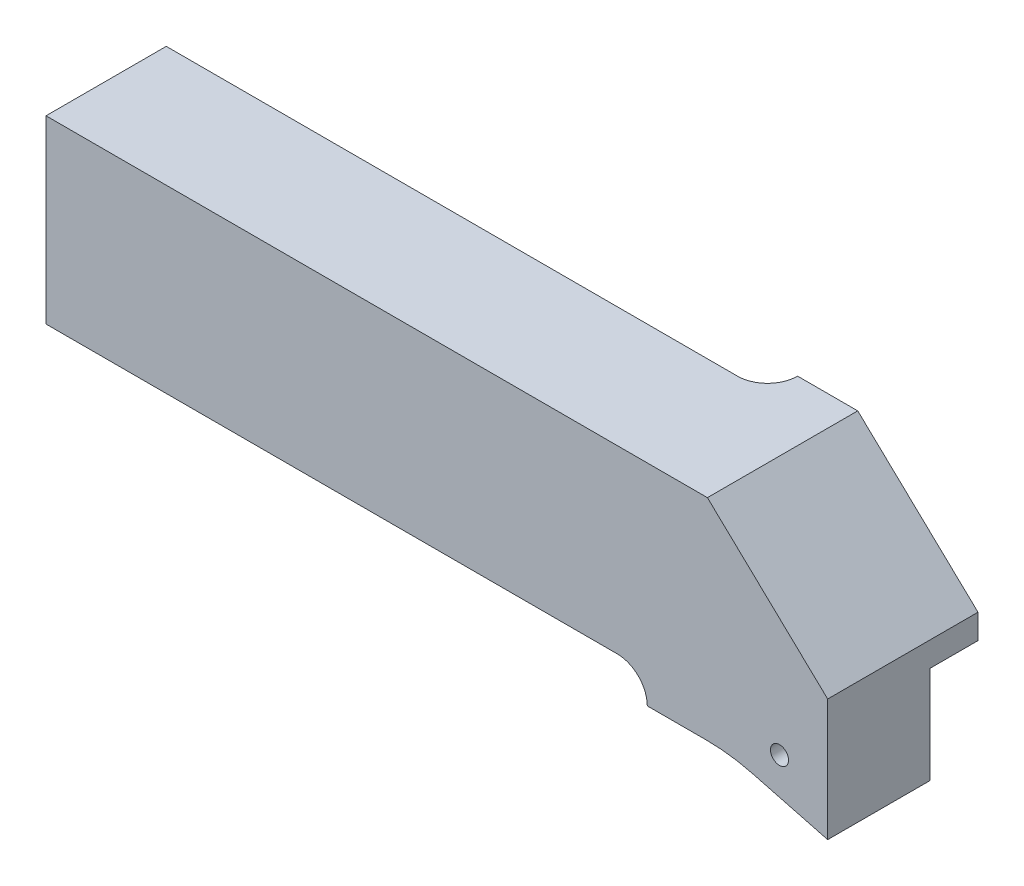
SolidWorks part; units mm, degrees
ref_plane "前视基准面" through (0, 0, 0) normal (0, 0, 1) x (1, 0, 0)
ref_plane "上视基准面" through (0, 0, 0) normal (0, 1, 0) x (1, 0, 0)
ref_plane "右视基准面" through (0, 0, 0) normal (1, 0, 0) x (0, 0, -1)
sketch "草图1" plane through (0, 0, 0) normal (0, 0, 1) x (1, 0, 0)
  line L1 (-40, 15) -> (60, 15)
  line L2 (-40, 15) -> (-40, -15)
  line L3 (-40, -15) -> (60, -15)
  line L4 (60, 15) -> (60, -15)
  point P0 (0, 0)
  dimension "D1" = 100
  dimension "D2" = 30
  dimension "D3" = 60
extrude "凸台-拉伸1" add sketch "草图1" along normal blind 20
sketch "草图2" plane through (0, 0, 20) normal (0, 0, 1) x (1, 0, 0)
  line L0 (60, 15) -> (70, 15)
  line L1 (60, 15) -> (60, -20)
  line L2 (60, -20) -> (69.8435, -20)
  line L3 (90, -20) -> (90, -4)
  line L4 (90, -4) -> (70, 15)
  line L5 (90, -24.2608) -> (90, -20)
  line L6 (77.4304, -20.9752) -> (90, -24.2608)
  arc A0 (69.8435, -20) -> (77.4304, -20.9752) centre (69.8435, -50) cw
  dimension "D4" = 30
  dimension "D1" = 35
  dimension "D2" = 10
  dimension "D3" = 30
  dimension "D5" = 16
extrude "凸台-拉伸2" add sketch "草图2" against normal blind 25
fillet "圆角2" radius 5 2 edges
sketch "草图4" plane through (0, 0, -5) normal (0, 0, -1) x (-1, 0, 0)
  line L0 (-90, -8.096) -> (-75, -8.9288)
  line L1 (-90, -24.2608) -> (-90, -4) construction
  line L2 (-75, -8.9288) -> (-75, -20.4465)
  line L10 (-90, -24.2608) -> (-90, -4)
  line L11 (-77.4304, -20.9752) -> (-90, -24.2608)
  line L12 (-90, -24.2608) -> (-90, -8.096)
  line L13 (-77.4304, -20.9752) -> (-90, -24.2608)
  arc A1 (-69.8435, -20) -> (-77.4304, -20.9752) centre (-69.8435, -50) ccw construction
  arc A5 (-69.8435, -20) -> (-77.4304, -20.9752) centre (-69.8435, -50) ccw
  arc A6 (-75, -20.4465) -> (-77.4304, -20.9752) centre (-69.8435, -50) ccw
  dimension "D1" = 0
  dimension "D2" = 11.5
  dimension "D3" = 16.1648
extrude "切除-拉伸1" cut sketch "草图4" against normal blind 8
sketch "草图5" plane through (0, 0, 3) normal (0, 0, -1) x (-1, 0, 0)
  line L0 (-75, -8.9288) -> (-90, -24.2608) construction
  circle A0 centre (-81.9932, -16.0768) radius 1.5
  dimension "D1" = 3
  dimension "D2" = 10
extrude "切除-拉伸2" cut sketch "草图5" against normal through all
cosmetic thread "装饰螺纹线1" parameters "D2"=9
